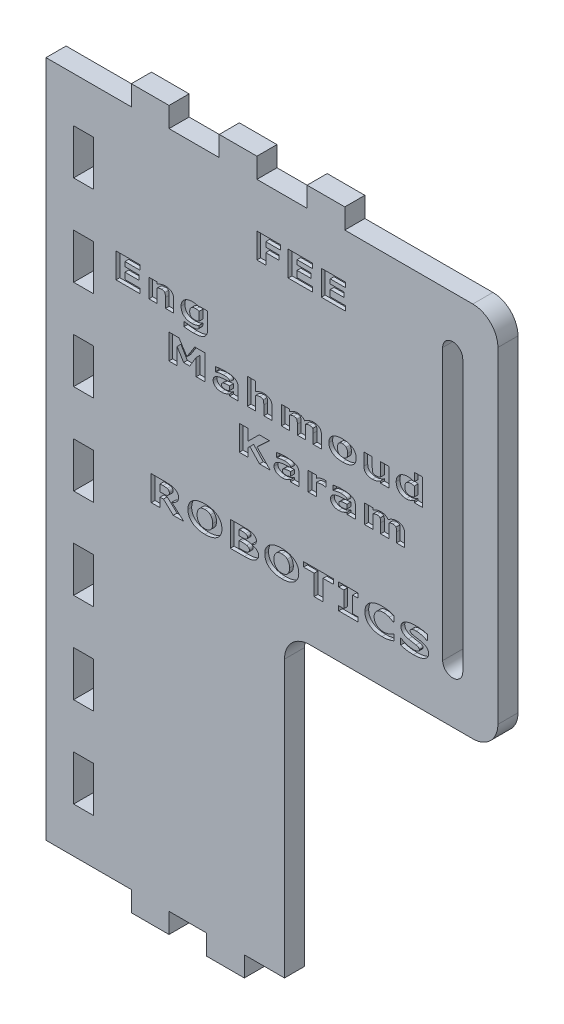
SolidWorks part; units mm, degrees
material "Beech"
ref_plane "Front" through (0, 0, 0) normal (0, 0, 1) x (1, 0, 0)
ref_plane "Top" through (0, 0, 0) normal (0, 1, 0) x (1, 0, 0)
ref_plane "Right" through (0, 0, 0) normal (1, 0, 0) x (0, 0, -1)
sketch "Sketch1" plane through (0, 0, 0) normal (0, 0, 1) x (1, 0, 0)
  line L25 (0, 0) -> (0, -120) construction
  line L28 (85, 0) -> (-95, 0) construction
  line L30 (85, 150) -> (-95, -120) construction
  line L31 (85, -120) -> (-95, 150) construction
  line L32 (-95, -120) -> (-95, 150) construction
  line L33 (85, 150) -> (-95, 150) construction
  line L34 (85, -120) -> (85, 150) construction
  line L35 (85, -120) -> (-95, -120) construction
  line L37 (-95, -120) -> (-95, 150)
  line L38 (0, -120) -> (-95, -120)
  line L39 (0, -10) -> (0, -120)
  line L40 (75, 0) -> (10, 0)
  line L41 (85, 140) -> (85, 10)
  line L42 (-95, 150) -> (75, 150)
  arc A8 (75, 150) -> (85, 140) centre (75, 140) cw
  arc A9 (85, 10) -> (75, 0) centre (75, 10) cw
  arc A10 (10, 0) -> (0, -10) centre (10, -10) ccw
  dimension "D2" = 10
  dimension "D1" = 180
  dimension "D3" = 85
  dimension "D4" = 150
  dimension "D5" = 120
extrude "Boss-Extrude1" add sketch "Sketch1" along normal blind 8 contours A8 L41 A9 L40 A10 L39 L38 L37 L42
sketch "Sketch3" plane through (0, 0, 8) normal (0, 0, 1) x (1, 0, 0)
  text T0 "        FEE\r\n\r\nEng\r\n   Mahmoud\r\n       Karam\r\n\r\n  ROBOTICS" font "Tahoma" height 10
extrude "Cut-Extrude1" cut sketch "Sketch3" against normal blind 1.5
sketch "Sketch4" plane through (0, 0, 8) normal (0, 0, 1) x (1, 0, 0)
  line L0 (0, -120) -> (-95, -120) construction
  line L1 (-84, -102) -> (-76, -102)
  line L2 (-84, -102) -> (-84, -84)
  line L3 (-84, -84) -> (-76, -84)
  line L4 (-76, -102) -> (-76, -84)
  line L5 (-84, -102) -> (-76, -84) construction
  line L6 (-84, -84) -> (-76, -102) construction
  line L7 (-95, -120) -> (-95, 150) construction
  line L8 (-84, -48) -> (-76, -48)
  line L9 (-76, -66) -> (-76, -48)
  line L10 (-84, -66) -> (-76, -66)
  line L11 (-84, -66) -> (-84, -48)
  line L12 (-84, -12) -> (-76, -12)
  line L13 (-76, -30) -> (-76, -12)
  line L14 (-84, -30) -> (-76, -30)
  line L15 (-84, -30) -> (-84, -12)
  line L16 (-84, 24) -> (-76, 24)
  line L17 (-76, 6) -> (-76, 24)
  line L18 (-84, 6) -> (-76, 6)
  line L19 (-84, 6) -> (-84, 24)
  line L20 (-84, 60) -> (-76, 60)
  line L21 (-76, 42) -> (-76, 60)
  line L22 (-84, 42) -> (-76, 42)
  line L23 (-84, 42) -> (-84, 60)
  line L24 (-84, 96) -> (-76, 96)
  line L25 (-76, 78) -> (-76, 96)
  line L26 (-84, 78) -> (-76, 78)
  line L27 (-84, 78) -> (-84, 96)
  line L28 (-84, 132) -> (-76, 132)
  line L29 (-76, 114) -> (-76, 132)
  line L30 (-84, 114) -> (-76, 114)
  line L31 (-84, 114) -> (-84, 132)
  point P4 (-80, -93)
  dimension "D1" = 18
  dimension "D2" = 11
  dimension "D3" = 8
  dimension "D4" = 18
  dimension "D6" = 18
  dimension "D5" = 7
extrude "Cut-Extrude2" cut sketch "Sketch4" against normal through all
sketch "Sketch5" plane through (0, -120, 0) normal (0, -1, 0) x (1, 0, 0)
  line L0 (0, 0) -> (-95, 0) construction
  line L1 (-61, 0) -> (-46, 0)
  line L2 (-61, 0) -> (-61, 8)
  line L3 (-61, 8) -> (-46, 8)
  line L4 (-46, 0) -> (-46, 8)
  line L5 (-61, 0) -> (-46, 8) construction
  line L6 (-61, 8) -> (-46, 0) construction
  line L7 (0, 8) -> (-95, 8) construction
  line L8 (-95, 8) -> (-95, 0) construction
  line L9 (-31, 8) -> (-16, 8)
  line L10 (-16, 0) -> (-16, 8)
  line L11 (-31, 0) -> (-16, 0)
  line L12 (-31, 0) -> (-31, 8)
  line L17 (-1, 0) -> (14, 0) [skipped]
  line L18 (14, 0) -> (14, 8) [skipped]
  line L19 (-1, 8) -> (14, 8) [skipped]
  line L20 (-1, 0) -> (-1, 8) [skipped]
  point P4 (-53.5, 4)
  dimension "D1" = 15
  dimension "D2" = 34
  dimension "D4" = 15
  dimension "D3" = 3
extrude "Boss-Extrude2" add sketch "Sketch5" along normal blind 8
sketch "Sketch6" plane through (0, 150, 0) normal (0, 1, 0) x (1, 0, 0)
  line L0 (-95, -8) -> (75, -8) construction
  line L1 (-61, -8) -> (-46, -8)
  line L2 (-61, -8) -> (-61, 0)
  line L3 (-61, 0) -> (-46, 0)
  line L4 (-46, -8) -> (-46, 0)
  line L5 (-61, -8) -> (-46, 0) construction
  line L6 (-61, 0) -> (-46, -8) construction
  line L7 (-95, 0) -> (75, 0) construction
  line L8 (-95, -8) -> (-95, 0) construction
  line L9 (-26, 0) -> (-11, 0)
  line L10 (-11, -8) -> (-11, 0)
  line L11 (-26, -8) -> (-11, -8)
  line L12 (-26, -8) -> (-26, 0)
  line L13 (9, 0) -> (24, 0)
  line L14 (24, -8) -> (24, 0)
  line L15 (9, -8) -> (24, -8)
  line L16 (9, -8) -> (9, 0)
  point P4 (-53.5, -4)
  dimension "D1" = 34
  dimension "D2" = 15
  dimension "D3" = 3
extrude "Boss-Extrude3" add sketch "Sketch6" along normal blind 8
sketch "Sketch8" plane through (0, 0, 8) normal (0, 0, 1) x (1, 0, 0)
  line L5 (67, 129) -> (67, 21) construction
  line L6 (71, 129) -> (71, 21)
  line L7 (63, 129) -> (63, 21)
  line L8 (85, 140) -> (85, 10) construction
  line L11 (75, 0) -> (10, 0) construction
  arc A0 (71, 129) -> (63, 129) centre (67, 129) ccw
  arc A1 (63, 21) -> (71, 21) centre (67, 21) ccw
  point P2 (67, 75)
  point P9 (0, 0)
  dimension "D4" = 21
  dimension "D1" = 8
  dimension "D2" = 108
  dimension "D3" = 14
extrude "Cut-Extrude3" cut sketch "Sketch8" against normal through all
